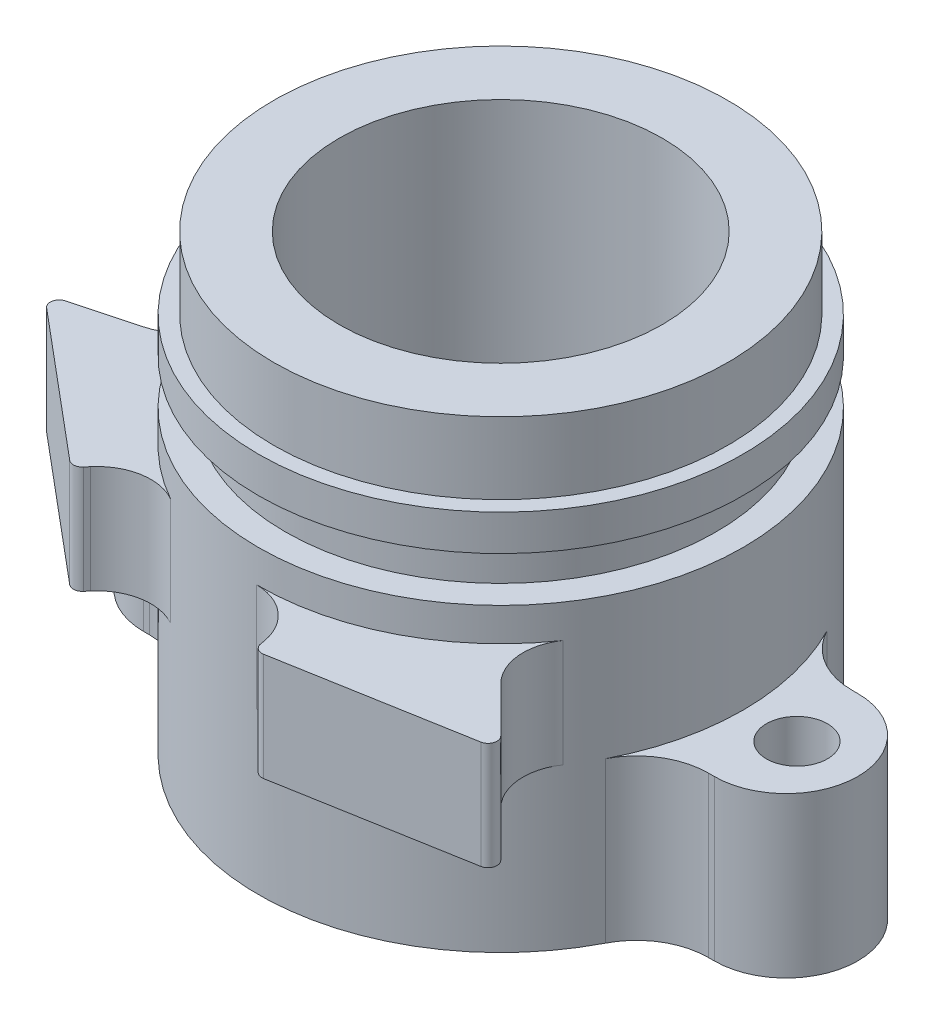
SolidWorks part; units mm, degrees
other "标注1"
sketch "草图16" plane through (-20.046, -4.9, -13.5) normal (-0.163, -0.9366, -0.3103) x (0.9815, -0.1218, -0.148)
material "ABS"
ref_plane "前视基准面" through (0, 0, 0) normal (0, 0, 1) x (1, 0, 0)
ref_plane "上视基准面" through (0, 0, 0) normal (0, 1, 0) x (1, 0, 0)
ref_plane "右视基准面" through (0, 0, 0) normal (1, 0, 0) x (0, 0, -1)
sketch "草图1" plane through (0, 0, 0) normal (0, 1, 0) x (1, 0, 0)
  circle A0 centre (0, 0) radius 9
  circle A1 centre (0, 0) radius 13.5
  dimension "D1" = 18
  dimension "D2" = 27
extrude "凸台-拉伸1" add sketch "草图1" along normal blind 16.35
sketch "草图2" plane through (0, 16.35, 0) normal (0, 1, 0) x (1, 0, 0)
  circle A0 centre (0, 0) radius 9
  circle A1 centre (0, 0) radius 12.65
  dimension "D1" = 18
  dimension "D2" = 25.3
extrude "凸台-拉伸2" add sketch "草图2" along normal blind 4
sketch "草图3" plane through (0, 16.35, 0) normal (0, 1, 0) x (1, 0, 0)
  circle A0 centre (0, 0) radius 13.5
  circle A1 centre (0, 0) radius 12
  dimension "D1" = 27
  dimension "D2" = 24
extrude "切除-拉伸1" cut sketch "草图3" against normal blind 2.5 from offset 2 offset against normal yes
sketch "草图5" plane through (0, 0, 0) normal (0, -1, 0) x (1, 0, 0)
  line L0 (-12.8938, 4) -> (-12.8938, -4)
  line L1 (-12.8938, 4) -> (-19.8938, 4)
  line L2 (-12.8938, -4) -> (-19.8938, -4)
  line L3 (-19.8938, 4) -> (-19.8938, -4)
  line L4 (0, 0) -> (-19.6563, 0) construction
  line L5 (0, 0) -> (0, 4.2417) construction
  line L6 (12.8938, -4) -> (19.8938, -4)
  line L7 (19.8938, 4) -> (19.8938, -4)
  line L8 (12.8938, 4) -> (19.8938, 4)
  line L9 (12.8938, 4) -> (12.8938, -4)
  circle A0 centre (0, 0) radius 9 construction
  circle A1 centre (0, 0) radius 13.5
  circle A2 centre (0, 0) radius 13.5
  circle A3 centre (0, 0) radius 9
  circle M8 centre (0, 0) radius 13.5
  circle M9 centre (0, 0) radius 9
  dimension "D2" = 7
  dimension "D3" = 8
  dimension "D1" = 0
extrude "凸台-拉伸3" add sketch "草图5" along normal blind 2.5 contours L9 L0 M8 M9 | L1 L3 L2 L0 | L8 L7 L6 L9 region at (0, 0, 13.1266)
sketch "草图6" plane through (0, 0, 0) normal (0, 1, 0) x (1, 0, 0)
  line L3 (-12.8938, 4) -> (-19.8938, 4)
  line L4 (-19.8938, 4) -> (-19.8938, -4)
  line L5 (-19.8938, -4) -> (-12.8938, -4)
  line L6 (-12.8938, 4) -> (-19.8938, 4)
  line L7 (-19.8938, 4) -> (-19.8938, -4)
  line L8 (-19.8938, -4) -> (-12.8938, -4)
  line L9 (12.8938, -4) -> (19.8938, -4)
  line L10 (19.8938, -4) -> (19.8938, 4)
  line L11 (19.8938, 4) -> (12.8938, 4)
  line L12 (12.8938, -4) -> (19.8938, -4)
  line L13 (19.8938, -4) -> (19.8938, 4)
  line L14 (19.8938, 4) -> (12.8938, 4)
  arc A1 (-12.8938, 4) -> (-12.8938, -4) centre (0, 0) ccw
  arc A2 (-12.8938, 4) -> (-12.8938, -4) centre (0, 0) ccw
  arc A3 (12.8938, -4) -> (12.8938, 4) centre (0, 0) ccw
  arc A4 (12.8938, -4) -> (12.8938, 4) centre (0, 0) ccw
  dimension "D1" = 0
  dimension "D2" = 0
extrude "凸台-拉伸4" add sketch "草图6" along normal blind 4
fillet "圆角1" radius 4 8 edges at (-12.8938, 0.75, -4) (12.8938, 0.75, 4) (-19.8938, 0.75, -4) (-19.8938, 0.75, 4) (-12.8938, 0.75, 4) (19.8938, 0.75, 4) (19.8938, 0.75, -4) (12.8938, 0.75, -4)
sketch "草图8" plane through (0, 4, 0) normal (0, 1, 0) x (1, 0, 0)
  line L0 (-20.8938, 0) -> (20.8938, 0) construction
  line L3 (0, 0) -> (0, -3.5186) construction
  circle A0 centre (-16.5, 0) radius 1.7
  circle A1 centre (16.5, 0) radius 1.7
  dimension "D1" = 3.4
  dimension "D2" = 33
extrude "切除-拉伸2" cut sketch "草图8" against normal through all both and the other way through all
sketch "草图9" plane through (0, 4, 0) normal (0, 1, 0) x (1, 0, 0)
  circle A0 centre (-16.5, 0) radius 2.75
  circle A1 centre (16.5, 0) radius 2.75
  dimension "D1" = 5.5
extrude "切除-拉伸3" [suppressed] cut sketch "草图9" against normal blind 2.2
sketch "草图10" plane through (0, -2.5, 0) normal (0, -1, 0) x (1, 0, 0)
  line L0 (-12.0208, -12.0208) -> (-17.1808, -6.8609)
  line L1 (5.8143, -15.9748) -> (12.459, -13.5563)
  line L2 (0, -17) -> (18.0461, -17) construction
  line L3 (0, -17) -> (0, -1.9182) construction
  line L5 (12.459, -13.5563) -> (10.5779, -8.388)
  line L6 (-12.0208, -12.0208) -> (-9.5459, -9.5459)
  line L7 (5.8143, -15.9748) -> (4.6173, -12.6859)
  line L8 (-17.1808, -6.8609) -> (-12.5373, -5.0066)
  circle A0 centre (0, 0) radius 17 construction
  arc A2 (-12.0068, -6.1714) -> (12.0068, -6.1714) centre (0, 0) ccw construction
  arc A6 (-12.0068, -6.1714) -> (-9.5459, -9.5459) centre (0, 0) ccw
  arc A7 (4.6173, -12.6859) -> (10.5779, -8.388) centre (0, 0) ccw
  arc A8 (-12.5373, -5.0066) -> (-9.5459, -9.5459) centre (0, 0) ccw
  arc A9 (4.6173, -12.6859) -> (10.5779, -8.388) centre (0, 0) ccw
  arc M15 (-15.5644, -4) -> (-12.0068, -6.1714) centre (-15.5644, -8) cw
  arc M16 (-12.0068, -6.1714) -> (12.0068, -6.1714) centre (0, 0) ccw
  dimension "D1" = 34
  dimension "D5" = 5
  dimension "D2" = 45
  dimension "D3" = 20
  dimension "D4" = 5.5
extrude "凸台-拉伸5" add sketch "草图10" against normal blind 5 from offset 8 contours L8 L0 L6 M16 M15 | A8 L8 M15 | L7 L1 L5 M16 region at (8.6761, -2.5, -12.6828) region at (-13.0813, -2.5, -8.3345) region at (-12.4919, -2.5, -5.3299) offset against normal yes
fillet "圆角2" [suppressed] radius 2
fillet "圆角3" [suppressed] radius 2
fillet "圆角4" radius 1 2 edges at (-12.0208, 8, -12.0208) (5.8143, 8, -15.9748)
sketch "草图11" plane through (0, 4, 0) normal (0, 1, 0) x (1, 0, 0)
  circle A0 centre (0, 0) radius 13.5 construction
  circle A1 centre (0, 0) radius 13.5
  circle A2 centre (0, 0) radius 25
  dimension "D1" = 50
extrude "切除-拉伸4" cut sketch "草图11" along normal blind 10
sketch "草图12" plane through (0, 4, 0) normal (0, 1, 0) x (1, 0, 0)
  line L0 (0, 24.299) -> (0, -20.4593) construction
  line L1 (0, 0) -> (-18.5767, -22.1388) construction
  line L2 (-10.9274, -13.0228) -> (-34.8065, 7.0142) construction
  line L3 (-10.9274, -13.0228) -> (-20.046, -5.3713)
  line L4 (-20.046, -5.3713) -> (-12.557, -3.3646)
  line L5 (-8.3562, -9.9586) -> (-10.9274, -13.0228)
  line L6 (-12.557, -3.3646) -> (0, 0) construction
  line L7 (0, 0) -> (2.952, -16.7417) construction
  line L8 (2.952, -16.7417) -> (30.8176, -11.8283) construction
  line L9 (14.6747, -14.6747) -> (0, 0) construction
  line L10 (14.6747, -14.6747) -> (2.952, -16.7417)
  line L11 (14.6747, -14.6747) -> (9.1924, -9.1924)
  line L12 (2.952, -16.7417) -> (2.2574, -12.8025)
  circle A0 centre (0, 0) radius 13.5 construction
  circle A1 centre (0, 0) radius 13.5
  circle A2 centre (0, 0) radius 17
  circle A3 centre (0, 0) radius 13
  point P6 (-10.9274, -13.0228)
  arc M16 (12.0068, -6.1714) -> (15.5644, -4) centre (15.5644, -8) cw
  dimension "D3" = 34
  dimension "D6" = 35
  dimension "D7" = 26
  dimension "D1" = 40
  dimension "D2" = 17
  dimension "D4" = 35
  dimension "D5" = 10
extrude "凸台-拉伸9" add sketch "草图12" along normal blind 6 contours L12 A2 L11 A1 M16 | A2 L10 L11 | L4 A2 L5 A1 | A2 L4 L3 region at (-12.7183, 4, 8.1024) region at (-16.5735, 4, 7.0626) region at (10.8218, 4, 14.4032) region at (6.9631, 4, 13.376)
fillet "圆角5" radius 3 4 edges at (9.5459, 7, 9.5459) (-13.04, 7, 3.4941) (-8.6776, 7, 10.3416) (2.3443, 7, 13.2949)
sketch "草图15" plane through (0, -2.5, 0) normal (0, -1, 0) x (1, 0, 0)
  line L4 (-15.5644, 4) -> (-15.8938, 4)
  line L5 (-15.8938, -4) -> (-15.5644, -4)
  line L6 (15.5644, -4) -> (15.8938, -4)
  line L7 (15.8938, 4) -> (15.5644, 4)
  line L8 (-15.5644, 4) -> (-15.8938, 4)
  line L9 (-15.8938, -4) -> (-15.5644, -4)
  line L10 (15.5644, -4) -> (15.8938, -4)
  line L11 (15.8938, 4) -> (15.5644, 4)
  circle A1 centre (0, 0) radius 9
  circle A2 centre (0, 0) radius 9
  circle A3 centre (-16.5, 0) radius 1.7
  circle A4 centre (-16.5, 0) radius 1.7
  circle A5 centre (16.5, 0) radius 1.7
  circle A6 centre (16.5, 0) radius 1.7
  arc A16 (-15.8938, 4) -> (-19.8938, 0) centre (-15.8938, 0) ccw
  arc A17 (-19.8938, 0) -> (-15.8938, -4) centre (-15.8938, 0) ccw
  arc A18 (-12.0068, -6.1714) -> (-15.5644, -4) centre (-15.5644, -8) ccw
  arc A19 (-12.0068, -6.1714) -> (12.0068, -6.1714) centre (0, 0) ccw
  arc A20 (15.5644, -4) -> (12.0068, -6.1714) centre (15.5644, -8) ccw
  arc A21 (15.8938, -4) -> (19.8938, 0) centre (15.8938, 0) ccw
  arc A22 (19.8938, 0) -> (15.8938, 4) centre (15.8938, 0) ccw
  arc A23 (12.0068, 6.1714) -> (15.5644, 4) centre (15.5644, 8) ccw
  arc A24 (12.0068, 6.1714) -> (-12.0068, 6.1714) centre (0, 0) ccw
  arc A25 (-15.5644, 4) -> (-12.0068, 6.1714) centre (-15.5644, 8) ccw
  arc A26 (-15.8938, 4) -> (-19.8938, 0) centre (-15.8938, 0) ccw
  arc A27 (-19.8938, 0) -> (-15.8938, -4) centre (-15.8938, 0) ccw
  arc A28 (-12.0068, -6.1714) -> (-15.5644, -4) centre (-15.5644, -8) ccw
  arc A29 (-12.0068, -6.1714) -> (12.0068, -6.1714) centre (0, 0) ccw
  arc A30 (15.5644, -4) -> (12.0068, -6.1714) centre (15.5644, -8) ccw
  arc A31 (15.8938, -4) -> (19.8938, 0) centre (15.8938, 0) ccw
  arc A32 (19.8938, 0) -> (15.8938, 4) centre (15.8938, 0) ccw
  arc A33 (12.0068, 6.1714) -> (15.5644, 4) centre (15.5644, 8) ccw
  arc A34 (12.0068, 6.1714) -> (-12.0068, 6.1714) centre (0, 0) ccw
  arc A35 (-15.5644, 4) -> (-12.0068, 6.1714) centre (-15.5644, 8) ccw
  dimension "D1" = 0
  dimension "D2" = 0
  dimension "D3" = 0
  dimension "D4" = 0
extrude "凸台-拉伸10" add sketch "草图15" along normal blind 2.4
fillet "圆角6" radius 0.5 4 edges at (-20.046, 7, 5.3713) (14.6747, 7, 14.6747) (2.952, 7, 16.7417) (-10.9274, 7, 13.0228)
